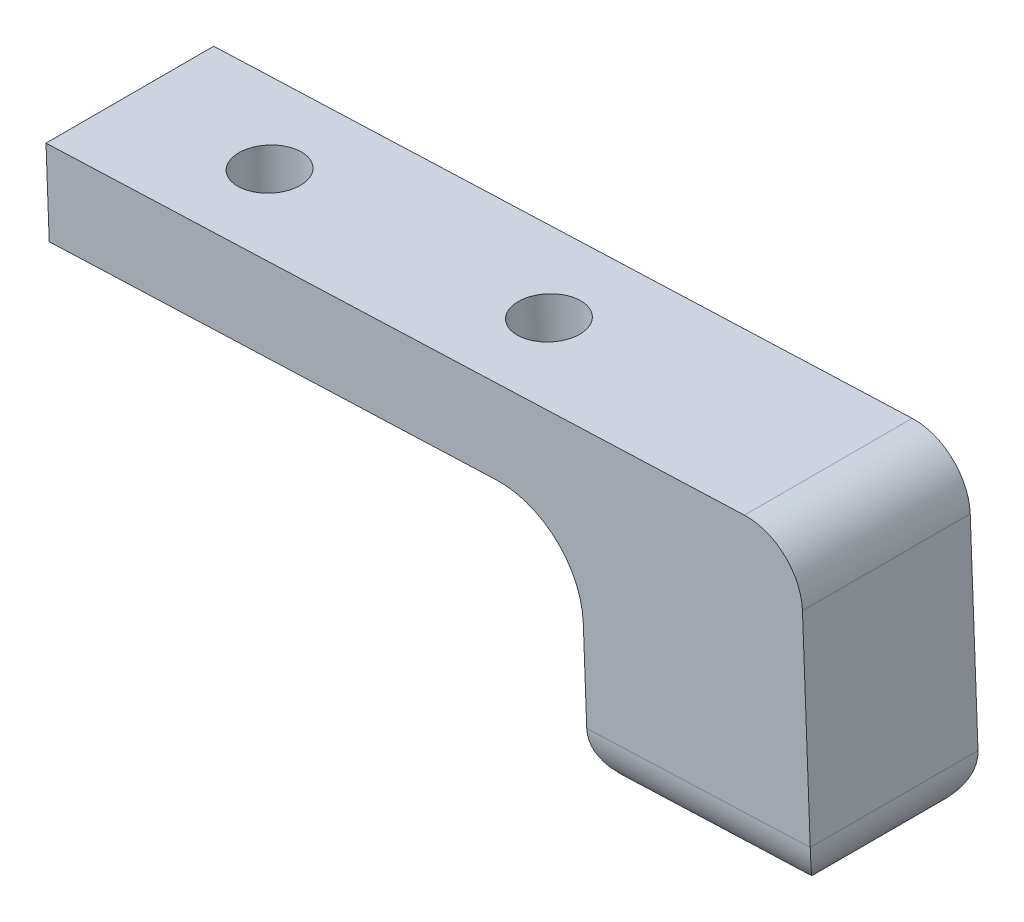
SolidWorks part; units mm, degrees
ref_plane "Front Plane" through (0, 0, 0) normal (0, 0, 1) x (1, 0, 0)
ref_plane "Top Plane" through (0, 0, 0) normal (0, 1, 0) x (1, 0, 0)
ref_plane "Right Plane" through (0, 0, 0) normal (1, 0, 0) x (0, 0, -1)
sketch "Sketch1" plane through (-0.4272, 11.0539, 0) normal (0.0386, -0.9993, 0) x (0.9993, 0.0386, 0)
  line L10 (-27.2546, 108) -> (-18.4546, 108) construction
  line L11 (-27.2546, 108) -> (-18.4546, 108)
  line L12 (-18.4546, 102) -> (-27.2546, 102) construction
  line L13 (-18.4546, 102) -> (-27.2546, 102)
  line L14 (-27.2546, 108) -> (-34.2546, 108)
  line L15 (-34.2546, 108) -> (-34.2546, 102)
  line L16 (-34.2546, 102) -> (-27.2546, 102)
  line L17 (-18.4546, 102) -> (-7.2546, 102)
  line L18 (-7.2546, 102) -> (-7.2546, 108)
  line L19 (-7.2546, 108) -> (-18.4546, 108)
  circle A0 centre (-19.2546, 105) radius 1.1 construction
  circle A1 centre (-29.2546, 105) radius 1.1 construction
  circle A2 centre (-19.2546, 105) radius 1.1
  circle A3 centre (-29.2546, 105) radius 1.1
  dimension "D1" = 5
  dimension "D2" = 12
extrude "Boss-Extrude1" add sketch "Sketch1" along normal blind 3
sketch "Sketch2" plane through (-0.3114, 8.0562, 0) normal (0.0386, -0.9993, 0) x (0.9993, 0.0386, 0)
  line L0 (-34.2546, 102) -> (-7.2546, 102) construction
  line L1 (-7.2546, 108) -> (-15.2546, 108)
  line L2 (-7.2546, 108) -> (-7.2546, 102)
  line L3 (-7.2546, 102) -> (-15.2546, 102)
  line L4 (-15.2546, 108) -> (-15.2546, 102)
  dimension "D1" = 8
extrude "Boss-Extrude2" add sketch "Sketch2" along normal blind 8.2
fillet "Fillet1" radius 2 4 edges at (-11.2409, -0.5724, 102) (-15.2379, -0.7269, 105) (-11.2409, -0.5724, 108) (-7.2439, -0.4179, 105)
fillet "Fillet2" radius 3 1 edges at (-15.5546, 7.467, 105)
fillet "Fillet6" radius 2 1 edges at (-7.6764, 10.7737, 105)
sketch "Sketch3" plane through (-0.3114, 8.0562, 0) normal (0.0386, -0.9993, 0) x (0.9993, 0.0386, 0)
  circle A2 centre (-29.2546, 105) radius 1.1 construction
  circle A3 centre (-29.2546, 105) radius 1.1
  circle A4 centre (-29.2546, 105) radius 2.25
  dimension "D1" = 4.5
extrude "Cut-Extrude1" cut sketch "Sketch3" against normal blind 1.5
